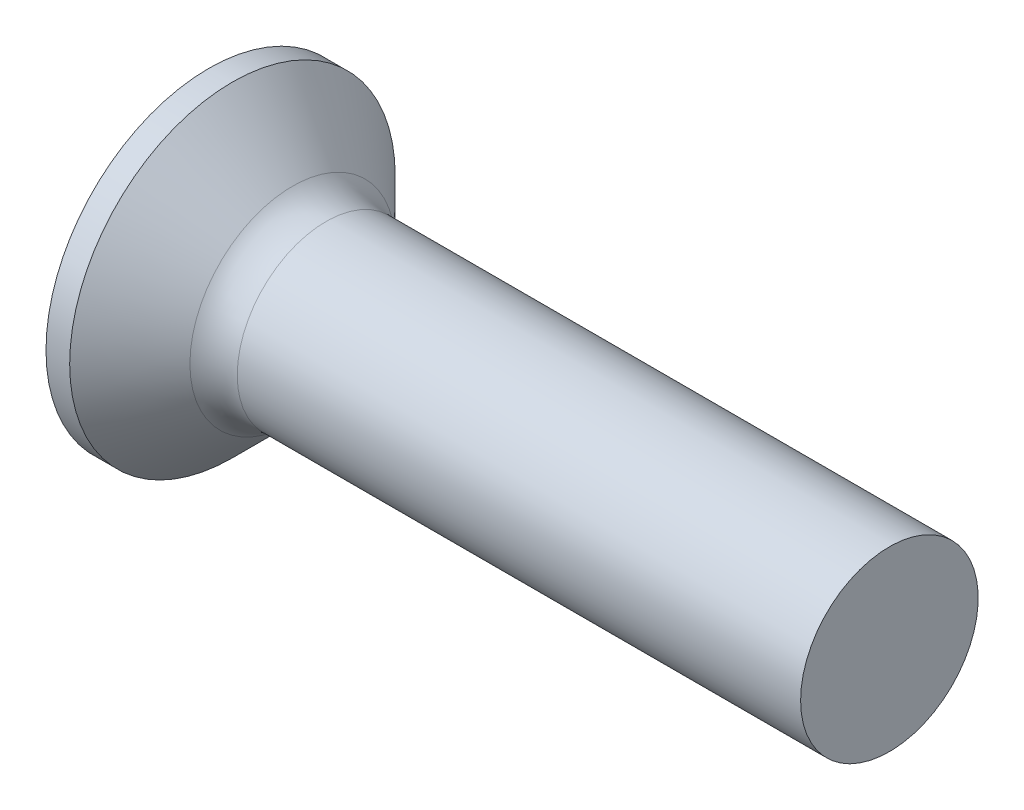
SolidWorks part; units mm, degrees
revolve "Base-Revolve" add sketch "BodySke"
sketch "BodySke" plane through (0, 0, 0) normal (0, 0, 1) x (1, 0, 0)
  line L0 (0, 0) -> (0, 2.75)
  line L1 (0, 2.75) -> (0.4, 2.75)
  line L2 (1.65, 1.5) -> (11.5, 1.5)
  line L3 (11.5, 1.5) -> (11.5, 0)
  line L4 (11.5, 0) -> (0, 0)
  line L5 (-6.35, 0) -> (82.55, 0) construction
  line L6 (1.65, -1.5) -> (11.5, -1.5) construction
  line L7 (0.4, -2.75) -> (1.65, -1.5) construction
  line L8 (0.4, 2.75) -> (1.65, 1.5)
  line L9 (0, -2.75) -> (0.4, -2.75) construction
  line L10 (2.15, 3.0875) -> (2.15, -6.4375) construction
  line L11 (7.5, 6.35) -> (7.5, -3.175) construction
  dimension "Diameter" = 3
  dimension "D6" = 0.4
cosmetic thread "ThreadCosmetic" [suppressed]
fillet "Fillet1" radius 0.8 1 edges at (1.65, 0, 1.5)
ref_plane "Plane1" through (0, 0, 0) normal (0, 0, 1) x (1, 0, 0)
ref_plane "Plane2" through (0, 0, 0) normal (0, 1, 0) x (1, 0, 0)
ref_plane "Plane3" through (0, 0, 0) normal (1, 0, 0) x (0, 0, -1)
sketch "Sketch3" plane through (0, 0, 0) normal (-1, 0, 0) x (0, 0, 1)
  line L0 (-0.37, 1.5) -> (0.37, 1.5)
  line L1 (0.37, 1.5) -> (0.37, -1.5)
  line L2 (0.37, -1.5) -> (-0.37, -1.5)
  line L3 (-0.37, -1.5) -> (-0.37, 1.5)
  dimension "Cross_dia" = 3
  dimension "Cross_width" = 0.74
  dimension "D1" = 1.5
  dimension "D2" = 0.37
ref_plane "Plane4" through (2.01, 0, 0) normal (-1, 0, 0) x (0, 0, 1)
sketch "Sketch4" plane through (2.01, 0, 0) normal (-1, 0, 0) x (0, 0, 1)
  line L0 (-0.37, 0.4979) -> (0.37, 0.4979)
  line L3 (0.37, 0.4979) -> (0.37, -0.4979)
  line L4 (0.37, -0.4979) -> (-0.37, -0.4979)
  line L5 (-0.37, -0.4979) -> (-0.37, 0.4979)
  dimension "D2" = 0.9957
  dimension "D1" = 0.74
  dimension "D4" = 0.4979
  dimension "D3" = 0.37
loft "Recess" cut profiles "Sketch3", "Sketch4"
pattern_circular "RecPat" count 2 every 90 about axis through (0, 0, 0) along (1, 0, 0) of "Recess"
sketch "RecCorSke" plane through (0, 0, 0) normal (0, 0, 1) x (1, 0, 0)
  line L0 (-3.175, 0) -> (15.875, 0) construction
  line L2 (0, 0) -> (0, 0.6966)
  line L3 (0, 0.6966) -> (2.01, 0.556)
  line L4 (2.01, 0.556) -> (2.1907, 0)
  line L5 (2.1907, 0) -> (0, 0)
revolve "RecessCore" cut sketch "RecCorSke" angle 360 about L0
sketch "ThdSchSke" plane through (0, 0, 0) normal (0, 0, 1) x (1, 0, 0)
  line L0 (7.5, -1.2195) -> (7.3036, -1.5)
  line L1 (7.5, -1.2195) -> (7.6964, -1.5)
  line L2 (7.6964, -1.5) -> (7.6964, -1.875)
  line L3 (-3.175, 0) -> (5.1513, 0) construction
  line L5 (7.6964, -1.875) -> (7.3036, -1.875)
  line L6 (7.3036, -1.875) -> (7.3036, -1.5)
  line L7 (0, 2.75) -> (0, -2.75) construction
  dimension "Diameter" = 3
  dimension "Thread_minor" = 2.439
  dimension "Start" = 7.5
revolve "ThreadSchematic" [suppressed] cut sketch "ThdSchSke" angle 360 about L3
pattern_linear "ThdSchPat" [suppressed]
equation "\"D1@Sketch3\" = \"Cross_dia@Sketch3\" / 2"
equation "\"D2@Sketch3\" = \"Cross_width@Sketch3\" / 2"
equation "\"Depth@RecCorSke\" = \"Cross_depth@Plane4\""
equation "\"D1@Sketch4\" = \"Cross_width@Sketch3\""
equation "\"D2@Sketch4\" = \"Cross_dia@Sketch3\" - 2.0 * \"Cross_depth@Plane4\" * tan(26.5  * 0.017453292)"
equation "\"D3@Sketch4\" = \"D1@Sketch4\" / 2"
equation "\"D4@Sketch4\" = \"D2@Sketch4\" / 2"
equation "\"Thread_length@ThreadCosmetic\" = ((sgn( (\"Length@BodySke\" - \"Advance@BodySke\" * 1.0 - \"Head_ht@BodySke\" ) - \"Thread_nom@BodySke\" )-1)*( (\"Length@BodySke\" - \"Advance@BodySke\" * 1.0 - \"Head_ht@BodySke\" ) - \"Thread_nom@BodySke\" ))/-2+ \"Thread_nom@BodySke\""
equation "\"Thread_minor@ThdSchSke\" = \"Thread_minor@ThreadCosmetic\""
equation "\"Diameter@ThdSchSke\" = \"Diameter@BodySke\""
equation "\"Overcut@ThdSchSke\" = \"Diameter@BodySke\" * 1.25"
equation "\"Start@ThdSchSke\" = 0.000001 + \"Length@BodySke\" - \"Thread_length@ThreadCosmetic\"  '---Countersunk---"
equation "\"Num_threads@ThdSchPat\" = int( \"Thread_length@ThreadCosmetic\" / \"Advance@BodySke\" + 0.999 )  + 1"
equation "\"Advance@ThdSchPat\" = \"Thread_length@ThreadCosmetic\" /  (\"Num_threads@ThdSchPat\" - 1) 'relax it"
